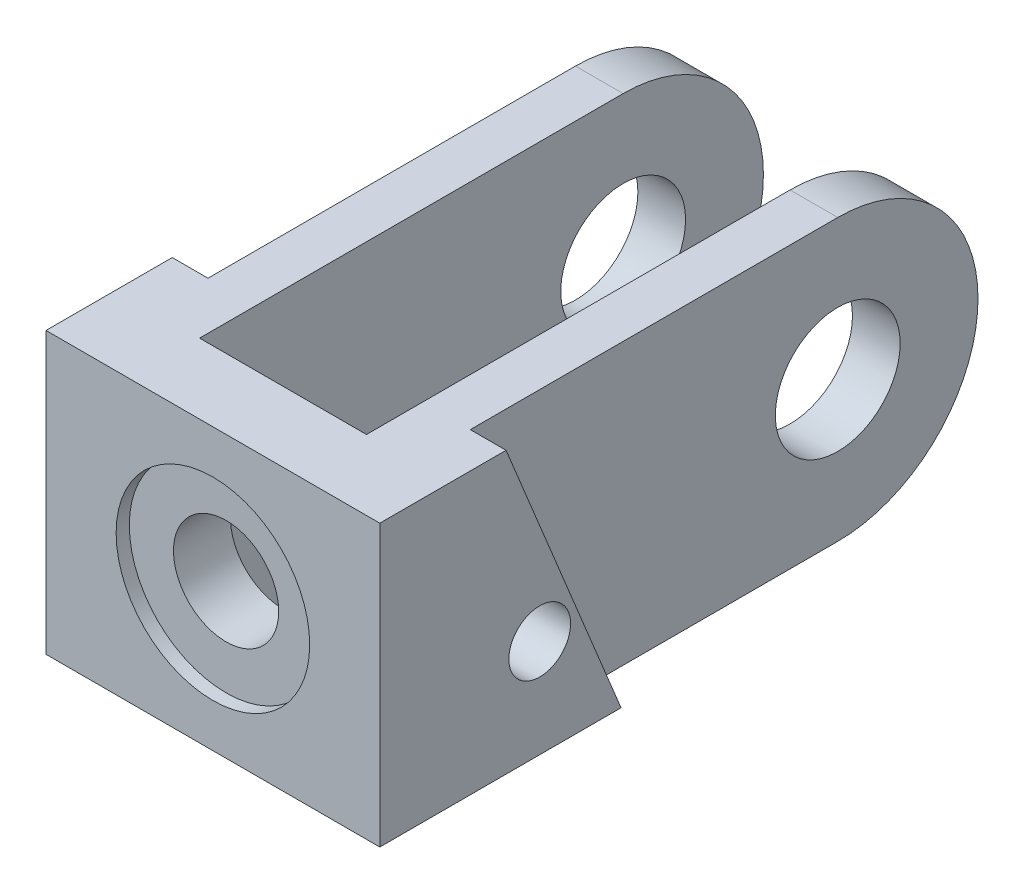
SolidWorks part; units mm, degrees
ref_plane "Front Plane" through (0, 0, 0) normal (0, 0, 1) x (1, 0, 0)
ref_plane "Top Plane" through (0, 0, 0) normal (0, 1, 0) x (1, 0, 0)
ref_plane "Right Plane" through (0, 0, 0) normal (1, 0, 0) x (0, 0, -1)
sketch "Sketch1" plane through (0, 0, 0) normal (1, 0, 0) x (0, 0, -1)
  line L0 (0, 0) -> (43.688, 0)
  line L1 (43.688, 0) -> (22.86, 50.8)
  line L2 (22.86, 50.8) -> (0, 50.8)
  line L3 (0, 50.8) -> (0, 0)
  line L4 (12.7, 50.8) -> (12.7, 0)
  line L5 (22.86, 50.8) -> (89.408, 50.8)
  line L6 (43.688, 0) -> (89.408, 0)
  circle A0 centre (28.956, 17.78) radius 5.588
  circle A1 centre (89.408, 25.4) radius 25.4
  circle A2 centre (89.408, 25.4) radius 11.303
  circle A3 centre (89.408, 25.4) radius 10.922
  dimension "D6" = 11.176
  dimension "D9" = 50.8
  dimension "D10" = 22.606
  dimension "D11" = 21.844
  dimension "D1" = 22.86
  dimension "D2" = 43.688
  dimension "D3" = 50.8
  dimension "D4" = 28.956
  dimension "D5" = 17.78
  dimension "D7" = 12.7
  dimension "D8" = 60.452
extrude "Boss-Extrude1" add sketch "Sketch1" along normal blind 15.113 contours L4 L2 L3 L0 region at (0, 25.4, -6.35)
extrude "Boss-Extrude2" add sketch "Sketch1<3>" along normal blind 8.636 from offset 15.113 contours A1 L5 L1 L6 | A1 A2 | L2 L4 L0 L1 A0 | L4 L2 L3 L0 region at (0, 25.4, -6.35) region at (0, 21.4598, -23.3383) region at (0, 27.8367, -51.311) region at (0, 25.4, -64.7264)
sketch "Sketch1<3>" plane through (0, 0, 0) normal (1, 0, 0) x (0, 0, -1) same geometry as "Sketch1"
extrude "Boss-Extrude3" add sketch "Sketch1<4>" along normal blind 6.477 from offset 23.749 contours L2 L4 L0 L1 A0 | L4 L2 L3 L0 region at (0, 25.4, -6.35) region at (0, 21.4598, -23.3383)
sketch "Sketch1<4>" plane through (0, 0, 0) normal (1, 0, 0) x (0, 0, -1) same geometry as "Sketch1"
mirror "Mirror1" about plane through (0, 0, 0) normal (1, 0, 0) of "Boss-Extrude2", "Boss-Extrude3", "Boss-Extrude1"
sketch "Sketch2" plane through (0, 0, 0) normal (0, 0, 1) x (1, 0, 0)
  line L0 (30.226, 0) -> (-30.226, 0) construction
  circle A0 centre (0, 25.4) radius 9.525
  dimension "D2" = 19.05
  dimension "D1" = 25.4
extrude "Cut-Extrude1" cut sketch "Sketch2" against normal through all
sketch "Sketch3" plane through (0, 0, 0) normal (0, 0, 1) x (1, 0, 0)
  circle A0 centre (0, 25.4) radius 17.526
  dimension "D1" = 35.052
extrude "Cut-Extrude2" cut sketch "Sketch3" against normal blind 2.3876
